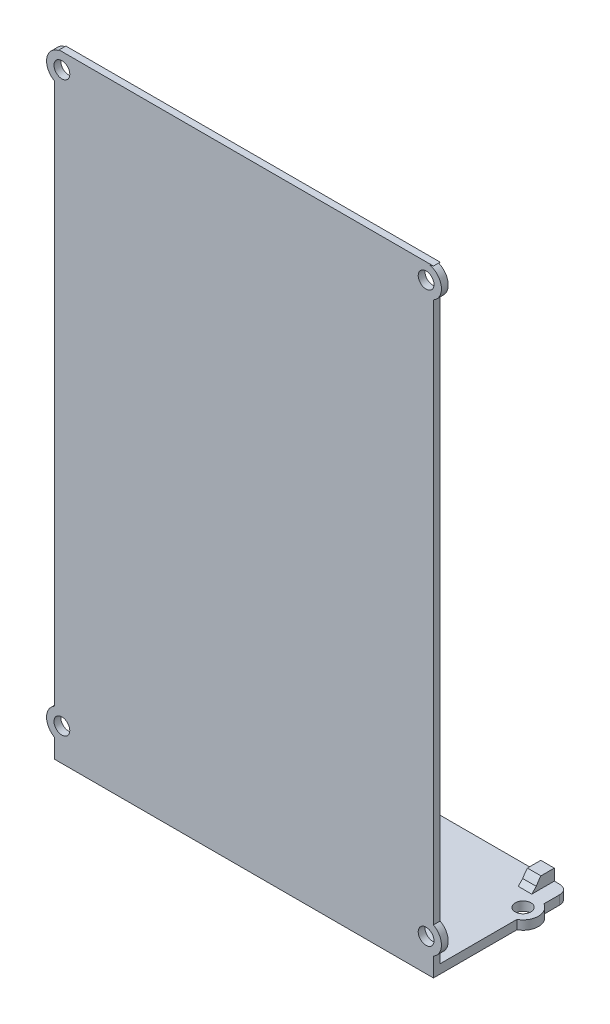
SolidWorks part; units mm, degrees
ref_plane "Front Plane" through (0, 0, 0) normal (0, 0, 1) x (1, 0, 0)
ref_plane "Top Plane" through (0, 0, 0) normal (0, 1, 0) x (1, 0, 0)
ref_plane "Right Plane" through (0, 0, 0) normal (1, 0, 0) x (0, 0, -1)
sketch "Sketch1" plane through (0, 0, 0) normal (0, 0, 1) x (1, 0, 0)
  line L0 (-38.75, -134.5) -> (38.75, -134.5)
  line L1 (-42, -126.5135) -> (-42, -6.4865) construction
  line L2 (-38.75, -132.4865) -> (-38.75, -134.5) construction
  line L3 (42, 0) -> (-42, 0) construction
  line L4 (42, -0.5135) -> (42, 0) construction
  line L5 (-38.75, -7) -> (-38.75, -126.5135) construction
  line L6 (38.75, -7) -> (-38.75, -7) construction
  line L28 (-42, -6.4865) -> (-42, -126.5135)
  line L29 (-42, -132.4865) -> (-42, -134.5)
  line L30 (-42, -134.5) -> (-38.75, -134.5)
  line L31 (-38.75, -134.5) -> (-38.1117, -132.0373) construction
  line L32 (-38.75, -126.5135) -> (-38.75, -7) construction
  line L33 (-38.75, -7) -> (38.75, -7) construction
  line L34 (38.75, -7) -> (38.75, -126.5135) construction
  line L35 (38.75, -132.4865) -> (38.75, -134.5) construction
  line L36 (38.75, -134.5) -> (42, -134.5)
  line L37 (42, -134.5) -> (42, -132.4865)
  line L38 (42, -126.5135) -> (42, -6.4865)
  line L39 (41.1041, -0.1791) -> (42, 0)
  line L40 (42, 0) -> (-41, 0)
  line L41 (-41, 0) -> (-41.193, -0.1999)
  circle A0 centre (-40.375, -129.5) radius 1.75
  circle A1 centre (40.375, -129.5) radius 1.75
  circle A2 centre (40.375, -3.5) radius 1.75
  circle A3 centre (-40.375, -3.5) radius 1.75
  arc A4 (-38.75, -132.4865) -> (-38.75, -126.5135) centre (-40.375, -129.5) ccw construction
  arc A5 (42, -6.4865) -> (42, -0.5135) centre (40.375, -3.5) ccw construction
  arc A12 (-42, -126.5135) -> (-42, -132.4865) centre (-40.375, -129.5) ccw
  arc A13 (-38.1117, -132.0373) -> (-38.75, -126.5135) centre (-40.375, -129.5) ccw construction
  arc A14 (38.75, -126.5135) -> (38.75, -132.4865) centre (40.375, -129.5) ccw construction
  arc A15 (42, -132.4865) -> (42, -126.5135) centre (40.375, -129.5) ccw
  arc A16 (42, -6.4865) -> (41.1041, -0.1791) centre (40.375, -3.5) ccw
  arc A17 (-41.193, -0.1999) -> (-42, -6.4865) centre (-40.375, -3.5) ccw
  dimension "D2" = 3.5
extrude "Boss-Extrude1" add sketch "Sketch1" along normal blind 1.5
sketch "Sketch2" plane through (-42, 0, 0) normal (-1, 0, 0) x (0, 0, 1)
  line L0 (1.5, -134.5) -> (1.5, -136.7)
  line L1 (1.5, -136.7) -> (-40, -136.7)
  line L2 (-40, -136.7) -> (-40, -134.7)
  line L3 (-40, -134.7) -> (0, -134.7)
  line L4 (0, -134.7) -> (0, -134.5)
  line L10 (0, -132.4865) -> (0, -134.5)
  line L11 (0, -134.5) -> (1.5, -134.5)
  line L12 (1.5, -134.5) -> (1.5, -132.4865)
  line L13 (1.5, -132.4865) -> (0, -132.4865)
  line L14 (0, -132.4865) -> (0, -134.5)
  line L16 (1.5, -134.5) -> (1.5, -132.4865)
  line L17 (1.5, -132.4865) -> (0, -132.4865)
  dimension "D1" = 2
  dimension "D2" = 0.2
  dimension "D4" = 40
  dimension "D3" = 0
extrude "Boss-Extrude2" add sketch "Sketch2" against normal up to surface (84 mm away) up to face at (42, -133.4933, 0.75)
sketch "Sketch3" plane through (-15, 0, 0) normal (1, 0, 0) x (0, 0, -1)
  line L0 (0, -119.7) -> (15, -134.7)
  line L1 (0, -126.5135) -> (0, -6.4865) construction
  line L2 (40, -134.7) -> (0, -134.7) construction
  line L3 (15, -134.7) -> (0, -134.7)
  line L4 (0, -134.7) -> (0, -119.7)
  dimension "D1" = 15
extrude "Boss-Extrude3" add sketch "Sketch3" along normal blind 1.5 and the other way blind 1.5
sketch "Sketch4" plane through (0, -136.7, 0) normal (0, -1, 0) x (1, 0, 0)
  line L0 (-42, -17.0135) -> (-42, -22.9865)
  line L1 (42, -17.0135) -> (42, -22.9865)
  line L9 (-42, -40) -> (-42, 1.5) construction
  line L10 (42, 1.5) -> (42, -40) construction
  line L11 (42, -17.0135) -> (40.375, -20) construction
  line L12 (40.375, -20) -> (42, -22.9865) construction
  arc A2 (-42, -17.0135) -> (-42, -22.9865) centre (-40.375, -20) ccw
  arc A3 (42, -22.9865) -> (42, -17.0135) centre (40.375, -20) ccw
  arc A4 (-42, -17.0135) -> (-42, -22.9865) centre (-40.375, -20) ccw construction
  arc A5 (42, -22.9865) -> (42, -17.0135) centre (40.375, -20) ccw construction
extrude "Boss-Extrude4" add sketch "Sketch4" against normal blind 2
sketch "Sketch5" plane through (0, -136.7, 0) normal (0, -1, 0) x (1, 0, 0)
  arc A0 (42, -22.9865) -> (42, -17.0135) centre (40.375, -20) ccw construction
  circle A1 centre (40.375, -20) radius 1.75
  circle A6 centre (-40.375, -20) radius 1.75
  arc A7 (-42, -17.0135) -> (-42, -22.9865) centre (-40.375, -20) ccw construction
  dimension "D1" = 3.5
  dimension "D2" = 3.5
extrude "Cut-Extrude1" cut sketch "Sketch5" against normal blind 2
sketch "Sketch6" plane through (0, -136.7, 0) normal (0, -1, 0) x (1, 0, 0)
  line L0 (-57.6714, -28.5) -> (65.3337, -28.5)
extrude "Cut-Extrude2" cut sketch "Sketch6" against normal through all and the other way through all
sketch "Sketch7" plane through (0, -136.7, 0) normal (0, -1, 0) x (1, 0, 0)
  line L0 (-42, -28.5) -> (42, -28.5) construction
  line L1 (-38.8, -28.5) -> (-35.8, -28.5)
  line L2 (-38.8, -28.5) -> (-38.8, -24.5)
  line L3 (-38.8, -24.5) -> (-35.8, -24.5)
  line L4 (-35.8, -28.5) -> (-35.8, -24.5)
  line L5 (-42, -25.7433) -> (-38.8, -25.7433) construction
  line L6 (38.8, -28.5) -> (35.8, -28.5)
  line L7 (38.8, -28.5) -> (38.8, -24.5)
  line L8 (38.8, -24.5) -> (35.8, -24.5)
  line L9 (35.8, -28.5) -> (35.8, -24.5)
  line L10 (-42, -28.5) -> (-42, -22.9865) construction
  line L11 (38.8, -24.5) -> (42, -24.5) construction
  line L12 (42, -22.9865) -> (42, -28.5) construction
  dimension "D1" = 3.2
  dimension "D2" = 3
  dimension "D3" = 4
extrude "Boss-Extrude6" add sketch "Sketch7" against normal blind 2.5 from surface at -2 starting at face at (-40.375, -134.7, -21.75)
fillet "Fillet1" radius 2 2 edges at (-42, -135.7, -28.5) (42, -135.7, -28.5)
chamfer "Chamfer1" distance 1 angle 45 4 edges at (-37.3, -132.2, -24.5) (37.3, -132.2, -24.5) (-37.3, -134.7, -24.5) (37.3, -134.7, -24.5)
fillet "Fillet2" radius 8 2 edges at (-37.3, -133.2, -24.5) (37.3, -133.2, -24.5)
sketch "Sketch8" plane through (0, -136.7, 0) normal (0, -1, 0) x (1, 0, 0)
  line L0 (-42, -17.0135) -> (-42, 1.5) construction
  line L1 (-10, -2.5) -> (16, -2.5)
  line L2 (-10, -2.5) -> (-10, -25.5)
  line L3 (-10, -25.5) -> (16, -25.5)
  line L4 (16, -2.5) -> (16, -25.5)
  line L5 (42, 1.5) -> (-42, 1.5) construction
  line L6 (-40, -28.5) -> (40, -28.5) construction
  dimension "D1" = 32
  dimension "D2" = 58
  dimension "D3" = 4
  dimension "D4" = 3
extrude "Cut-Extrude3" cut sketch "Sketch8" against normal blind 22.4262
